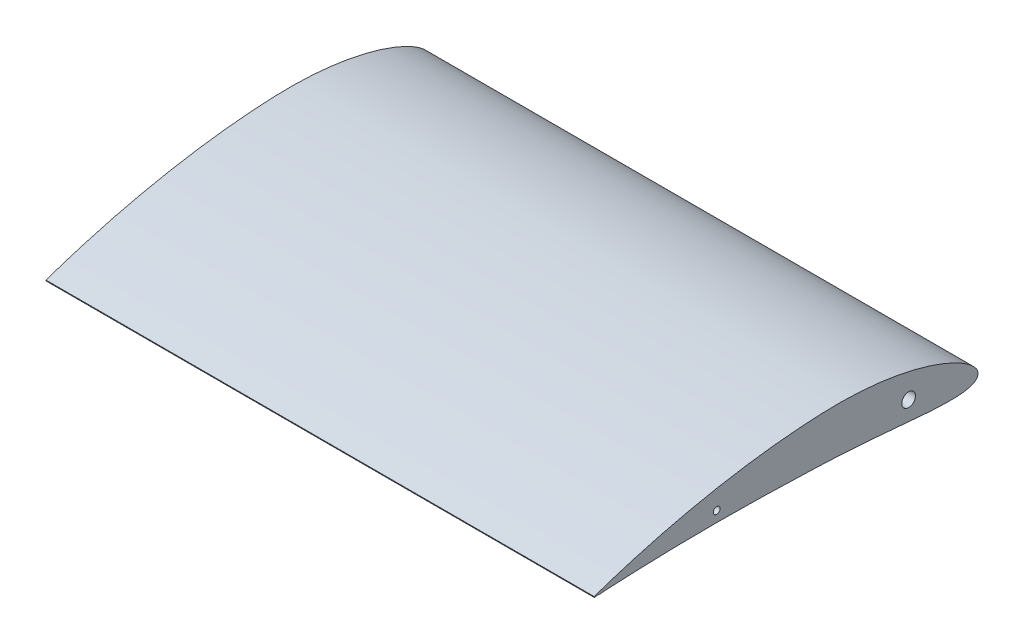
SolidWorks part; units mm, degrees
material "Thornel Mat VMA Foam Core"
ref_plane "Front Plane" through (0, 0, 0) normal (0, 0, 1) x (1, 0, 0)
ref_plane "Top Plane" through (0, 0, 0) normal (0, 1, 0) x (1, 0, 0)
ref_plane "Right Plane" through (0, 0, 0) normal (1, 0, 0) x (0, 0, -1)
curve "Curve1"
  spline degree 3 poles (0, 0.0012, 1.0003) (0, 0.0015, 0.9994) (0, 0.0028, 0.9958) (0, 0.0055, 0.9879) (0, 0.0099, 0.9747) (0, 0.0159, 0.9565) (0, 0.0233, 0.9333) (0, 0.0318, 0.9054) (0, 0.0411, 0.8731) (0, 0.051, 0.8366) (0, 0.0612, 0.7964) (0, 0.0713, 0.7528) (0, 0.0811, 0.7063) (0, 0.0903, 0.6574) (0, 0.0985, 0.6067) (0, 0.1057, 0.5546) (0, 0.1115, 0.5018) (0, 0.1158, 0.4488) (0, 0.1186, 0.3959) (0, 0.1189, 0.3436) (0, 0.1164, 0.2927) (0, 0.1112, 0.2442) (0, 0.1037, 0.1988) (0, 0.0942, 0.157) (0, 0.0831, 0.1194) (0, 0.0711, 0.0865) (0, 0.0584, 0.0585) (0, 0.0457, 0.0357) (0, 0.0334, 0.0184) (0, 0.0218, 0.0064) (0, 0.0108, -0.0005) (0, -0.0003, -0.0011) (0, -0.0092, 0.0055) (0, -0.0148, 0.017) (0, -0.0185, 0.0329) (0, -0.0204, 0.0533) (0, -0.0208, 0.0781) (0, -0.0198, 0.107) (0, -0.0176, 0.1398) (0, -0.0147, 0.176) (0, -0.0111, 0.2153) (0, -0.0074, 0.2574) (0, -0.0037, 0.3019) (0, -0.0005, 0.3484) (0, 0.002, 0.397) (0, 0.0037, 0.4471) (0, 0.0055, 0.4983) (0, 0.0069, 0.5496) (0, 0.0079, 0.6006) (0, 0.0085, 0.6505) (0, 0.0086, 0.699) (0, 0.0083, 0.7455) (0, 0.0076, 0.7894) (0, 0.0065, 0.8302) (0, 0.0053, 0.8675) (0, 0.0039, 0.9007) (0, 0.0027, 0.9296) (0, 0.0013, 0.9539) (0, 0.0006, 0.9727) (0, -0.0011, 0.9872) (0, 0, 0.9944) (0, -0.002, 0.9999) (0, -0.0005, 1) (0, 0, 1) knots 0 0 0 0 0.001372 0.005465 0.012235 0.021602 0.033461 0.047671 0.064081 0.082496 0.102719 0.124527 0.147676 0.171913 0.196978 0.222597 0.248497 0.274385 0.300041 0.32569 0.350525 0.37428 0.396711 0.417577 0.436654 0.453744 0.46868 0.481329 0.491631 0.499616 0.505546 0.510185 0.514824 0.520702 0.528516 0.538466 0.550543 0.564643 0.580638 0.598345 0.617584 0.638174 0.659922 0.682632 0.706121 0.730727 0.7557 0.780732 0.805564 0.829932 0.85357 0.876213 0.89761 0.917519 0.935698 0.951943 0.966047 0.97784 0.987174 0.993932 0.998018 0.999386 1 1 1 1
sketch "Sketch1" plane through (0, 0, 0) normal (1, 0, 0) x (0, 0, -1)
  line L0 (-354.7873, -0.0303) -> (-354.8762, 0.4104)
  line L1 (-354.7873, -0.0303) -> (0.8093, 1.5275) construction
  line L2 (0.8093, 1.5275) -> (0.7921, 5.4415) construction
  spline S1 degree 3 poles (-354.8762, 0.4104) (-354.5599, 0.5194) (-353.2997, 0.9536) (-350.4787, 1.9271) (-345.801, 3.4978) (-336.0241, 6.7216) (-319.6545, 11.7989) (-300.5983, 17.1306) (-282.4229, 21.7243) (-261.1758, 26.6516) (-238.6223, 31.1455) (-208.7748, 36.0048) (-183.9617, 39.0905) (-158.9023, 41.1132) (-140.0967, 42.1114) (-121.5167, 42.2289) (-103.4222, 41.3211) (-86.1884, 39.4787) (-70.0435, 36.8105) (-55.1998, 33.4329) (-41.8434, 29.5109) (-30.1305, 25.2201) (-20.187, 20.7343) (-12.1072, 16.2263) (-5.9269, 11.8553) (-1.6792, 7.7165) (0.7658, 3.7968) (0.9875, -0.1483) (-1.3511, -3.3089) (-5.4508, -5.2881) (-11.0873, -6.5875) (-18.3491, -7.2685) (-27.1638, -7.4049) (-37.4471, -7.0538) (-49.0831, -6.3019) (-61.9524, -5.238) (-75.9299, -3.9839) (-96.4067, -2.1536) (-117.9372, -0.4584) (-140.4848, 0.6745) (-158.2965, 1.2867) (-176.4839, 1.9179) (-200.672, 2.5862) (-224.5411, 2.9791) (-247.8302, 3.0285) (-264.3373, 2.9074) (-279.9331, 2.6564) (-294.438, 2.2829) (-307.6819, 1.8521) (-319.5134, 1.3711) (-329.7674, 0.9129) (-338.3889, 0.4268) (-345.077, 0.1915) (-350.2276, -0.4064) (-352.7802, -0.0354) (-354.7446, -0.7581) (-354.7772, -0.2025) (-354.7873, -0.0303) knots 0 0 0 0 0.001372 0.005465 0.012235 0.021602 0.047671 0.082496 0.102719 0.124527 0.171913 0.196978 0.248497 0.274385 0.300041 0.32569 0.350525 0.37428 0.396711 0.417577 0.436654 0.453744 0.46868 0.481329 0.491631 0.499616 0.505546 0.510185 0.514824 0.520702 0.528516 0.538466 0.550543 0.564643 0.580638 0.598345 0.617584 0.638174 0.682632 0.706121 0.730727 0.7557 0.780732 0.829932 0.85357 0.876213 0.89761 0.917519 0.935698 0.951943 0.966047 0.97784 0.987174 0.993932 0.998018 0.999386 1 1 1 1
  dimension "D1" = 355.6
extrude "Boss-Extrude1" add sketch "Sketch1" along normal blind 254 and the other way blind 254
sketch "Sketch2" plane through (-254, 0, 0) normal (-1, 0, 0) x (0, 0, 1)
  line L0 (195.725, 0) -> (-195.725, 0) construction
  line L1 (0, -27.2986) -> (0, 27.2986) construction
  circle A0 centre (63.5, 12.7) radius 6.35
  dimension "D1" = 12.7
  dimension "D2" = 12.7
  dimension "D3" = 63.5
extrude "Cut-Extrude1" cut sketch "Sketch2" against normal blind 101.6
mirror "Mirror1" about plane through (0, 0, 0) normal (1, 0, 0) of "Cut-Extrude1"
sketch "Sketch3" plane through (-254, 0, 0) normal (-1, 0, 0) x (0, 0, 1)
  line L0 (195.725, 0) -> (-195.725, 0) construction
  line L1 (0, -27.2986) -> (0, 27.2986) construction
  circle A0 centre (241.3, 12.7) radius 3.175
  dimension "D1" = 6.35
  dimension "D2" = 12.7
  dimension "D3" = 241.3
extrude "Cut-Extrude2" cut sketch "Sketch3" against normal blind 127
mirror "Mirror2" about plane through (0, 0, 0) normal (1, 0, 0) of "Cut-Extrude2"
